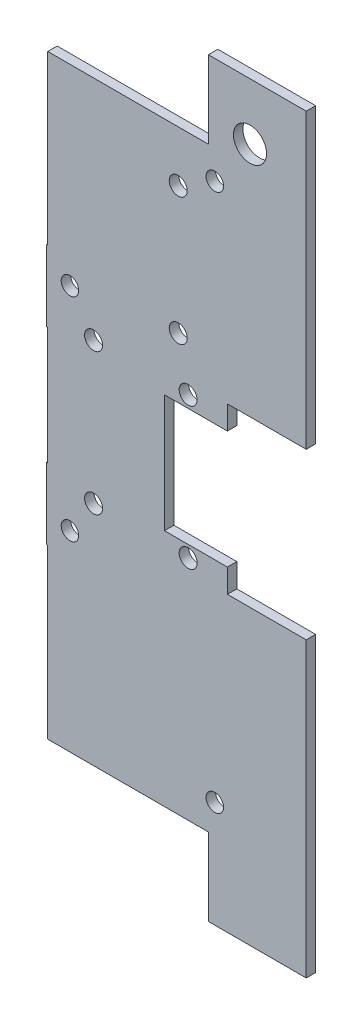
SolidWorks part; units mm, degrees
material "Thornel Mat VMA"
ref_plane "Front Plane" through (0, 0, 0) normal (0, 0, 1) x (1, 0, 0)
ref_plane "Top Plane" through (0, 0, 0) normal (0, 1, 0) x (1, 0, 0)
ref_plane "Right Plane" through (0, 0, 0) normal (1, 0, 0) x (0, 0, -1)
sketch "Sketch1" plane through (0, 0, 0) normal (0, 0, 1) x (1, 0, 0)
  line L0 (-2.9301, -104.5098) -> (-3.3149, -104.5098)
  line L1 (-3.3149, -72.8868) -> (-2.9301, -72.8868)
  line L78 (45.3299, -66.5368) -> (45.3299, -72.8868)
  line L79 (45.3299, -104.5098) -> (45.3299, -110.8598)
  line L80 (66.5174, -66.5368) -> (105.3971, 12.1397)
  line L81 (105.3971, 12.1397) -> (38.7094, 12.1397)
  line L88 (38.7094, 12.1397) -> (38.7094, -8.6883)
  line L89 (-2.9301, -8.6883) -> (38.7094, -8.6883)
  line L90 (-3.3149, -53.8368) -> (-2.9301, -53.8368)
  line L91 (-2.9301, -53.8368) -> (-2.9301, -8.6883)
  line L92 (-3.3149, -66.5368) -> (-3.3149, -53.8368)
  line L93 (-3.3149, -72.8868) -> (-3.3149, -66.5368)
  line L94 (-2.9301, -104.5098) -> (-2.9301, -72.8868)
  line L95 (-3.3149, -110.8598) -> (-3.3149, -104.5098)
  line L96 (66.5174, -110.8598) -> (105.3971, -189.5363)
  line L97 (105.3971, -189.5363) -> (38.7094, -189.5363)
  line L98 (38.7094, -189.5363) -> (38.7094, -168.7083)
  line L99 (-2.9301, -168.7083) -> (38.7094, -168.7083)
  line L106 (-3.3149, -110.8598) -> (-3.3149, -123.5598)
  line L107 (-3.3149, -123.5598) -> (-2.9301, -123.5598)
  line L108 (66.5174, -110.8598) -> (45.3299, -110.8598)
  line L109 (45.3299, -66.5368) -> (66.5174, -66.5368)
  line L110 (45.3299, -104.5098) -> (45.3299, -72.8868)
  line L111 (-2.9301, -123.5598) -> (-2.9301, -168.7083)
  circle A0 centre (90.6739, 2.6147) radius 2.3495
  circle A1 centre (41.9566, -16.4353) radius 2.3495
  circle A2 centre (3.0351, -60.1868) radius 2.3495
  circle A3 centre (3.0351, -117.2098) radius 2.3495
  circle A4 centre (41.9566, -160.9613) radius 2.3495
  circle A5 centre (90.6739, -180.0113) radius 2.3495
  circle A6 centre (51.4094, -3.1003) radius 4.445
  point P2 (90.6739, 2.6147)
  point P4 (41.9566, -16.4353)
  point P6 (3.0351, -60.1868)
  point P8 (3.0351, -117.2098)
  point P10 (41.9566, -160.9613)
  point P11 (90.6739, -180.0113)
  dimension "D2" = 4.699
  dimension "D5" = 8.89
  dimension "D1" = 66.6876
  dimension "D3" = 12.7
  dimension "D4" = 15.24
  dimension "D6" = 48.26
extrude "Boss-Extrude1" add sketch "Sketch1" along normal blind 2.54
sketch "Sketch2" plane through (0, 0, 2.54) normal (0, 0, 1) x (1, 0, 0)
  line L0 (-3.3149, -53.8368) -> (-3.3149, -72.8868) construction
  line L1 (45.3299, -66.5368) -> (66.5174, -66.5368) construction
  line L2 (45.3299, -88.6983) -> (-2.9301, -88.6983) construction
  line L3 (45.3299, -110.8598) -> (45.3299, -66.5368) construction
  line L4 (-2.9301, -72.8868) -> (-2.9301, -104.5098) construction
  circle A0 centre (9.3851, -69.7118) radius 2.413
  circle A2 centre (34.7851, -69.7118) radius 2.413
  circle A4 centre (34.7851, -107.6848) radius 2.413
  circle A6 centre (9.3851, -107.6848) radius 2.413
  dimension "D1" = 4.826
  dimension "D2" = 25.4
  dimension "D3" = 4.826
  dimension "D5" = 12.7
  dimension "D7" = 3.175
extrude "Cut-Extrude1" cut sketch "Sketch2" against normal through all
sketch "Sketch3" plane through (0, 0, 2.54) normal (0, 0, 1) x (1, 0, 0)
  line L0 (45.3299, -110.8598) -> (45.3299, -66.5368) construction
  line L1 (45.3299, -72.8868) -> (28.4351, -72.8868)
  line L2 (45.3299, -72.8868) -> (45.3299, -104.5098)
  line L3 (45.3299, -104.5098) -> (28.4351, -104.5098)
  line L4 (28.4351, -72.8868) -> (28.4351, -104.5098)
  line L5 (45.3299, -66.5368) -> (66.5174, -66.5368) construction
  line L6 (66.5174, -110.8598) -> (45.3299, -110.8598) construction
  circle A1 centre (9.3851, -69.7118) radius 2.413 construction
  dimension "D3" = 19.05
  dimension "D1" = 6.35
  dimension "D2" = 6.35
extrude "Cut-Extrude2" cut sketch "Sketch3" against normal through all
sketch "Sketch4" plane through (0, 0, 2.54) normal (0, 0, 1) x (1, 0, 0)
  line L0 (-2.9301, -168.7083) -> (38.7094, -168.7083) construction
  line L1 (27.4577, 15.7469) -> (40.2334, 15.7469)
  line L2 (27.4577, 15.7469) -> (27.4577, -8.6883)
  line L3 (27.4577, -8.6883) -> (40.2334, -8.6883)
  line L4 (40.2334, 15.7469) -> (40.2334, -8.6883)
  line L5 (0, -197.042) -> (40.2334, -197.042)
  line L6 (0, -197.042) -> (0, -168.7083)
  line L7 (0, -168.7083) -> (40.2334, -168.7083)
  line L8 (40.2334, -197.042) -> (40.2334, -168.7083)
  line L9 (38.7094, -168.7083) -> (38.7094, -189.5363) construction
  line L10 (38.7094, -8.6883) -> (-2.9301, -8.6883) construction
  dimension "D1" = 1.524
extrude "Cut-Extrude3" cut sketch "Sketch4" against normal through all
sketch "Sketch5" plane through (0, 0, 0) normal (0, 0, -1) x (-1, 0, 0)
  line L0 (2.9301, -8.6883) -> (2.9301, -53.8368) construction
  line L1 (-40.2334, -8.6883) -> (2.9301, -8.6883) construction
  circle A0 centre (-32.1219, -22.4043) radius 2.413
  circle A1 centre (-32.1219, -56.6943) radius 2.413
  dimension "D4" = 4.826
  dimension "D1" = 35.052
  dimension "D2" = 13.716
  dimension "D3" = 34.29
extrude "Cut-Extrude4" cut sketch "Sketch5" against normal through all
sketch "Sketch7" plane through (0, 0, 2.54) normal (0, 0, 1) x (1, 0, 0)
  line L0 (66.5174, -66.5368) -> (66.5174, 21.5221)
  line L1 (66.5174, 21.5221) -> (127.8208, 21.5221)
  line L2 (66.5174, -110.8598) -> (66.5174, -200.2563)
  line L3 (66.5174, -200.2563) -> (115.7822, -200.2563)
  line L4 (115.7822, -200.2563) -> (127.8208, 21.5221)
  line L5 (66.5174, -66.5368) -> (66.5174, -110.8598)
extrude "Cut-Extrude5" cut sketch "Sketch7" against normal through all both and the other way through all
